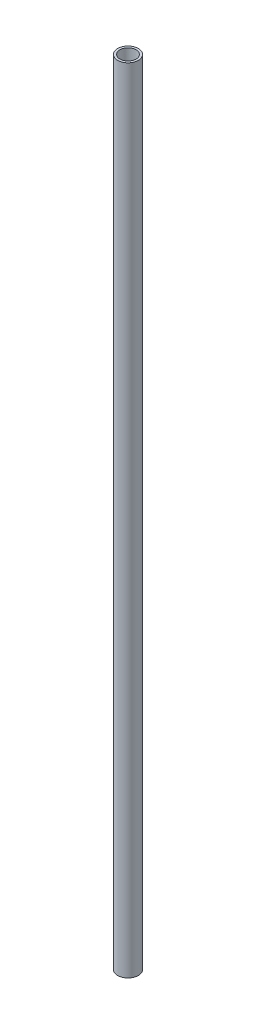
SolidWorks part; units mm, degrees
ref_plane "Front Plane" through (0, 0, 0) normal (0, 0, 1) x (1, 0, 0)
ref_plane "Top Plane" through (0, 0, 0) normal (0, 1, 0) x (1, 0, 0)
ref_plane "Right Plane" through (0, 0, 0) normal (1, 0, 0) x (0, 0, -1)
sketch "Sketch1" plane through (0, 0, 0) normal (0, 1, 0) x (1, 0, 0)
  circle A0 centre (0, 0) radius 7.9375
  circle A1 centre (0, 0) radius 6.2103
extrude "Boss-Extrude1" add sketch "Sketch1" along normal blind 609.6
